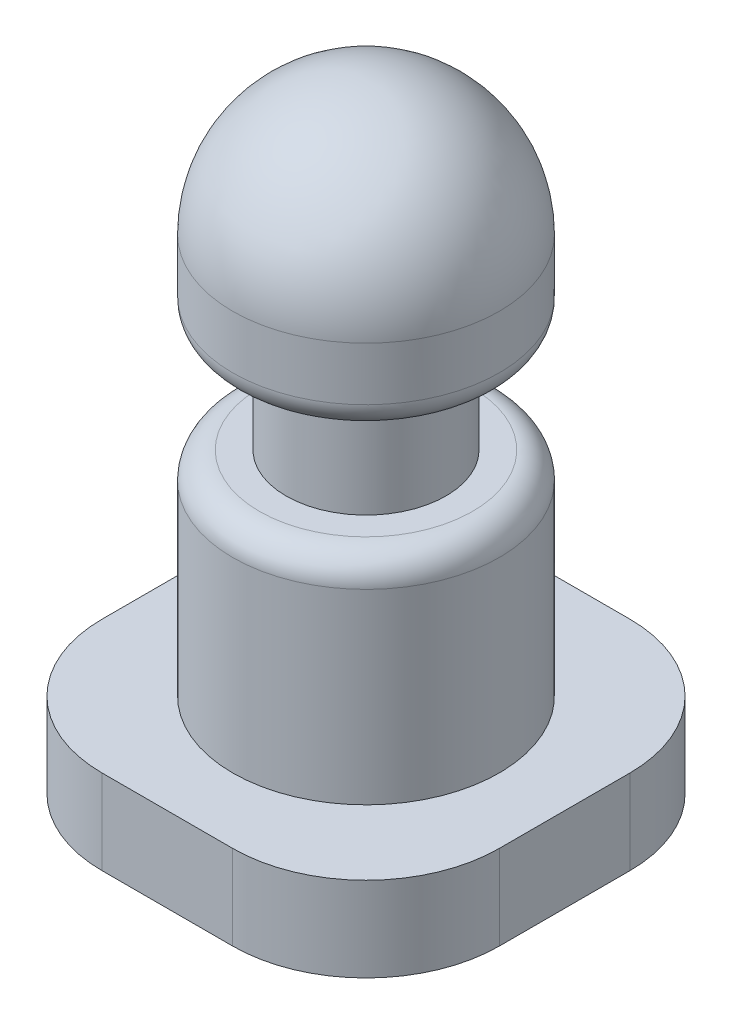
SolidWorks part; units mm, degrees
ref_plane "Front Plane" through (0, 0, 0) normal (0, 0, 1) x (1, 0, 0)
ref_plane "Top Plane" through (0, 0, 0) normal (0, 1, 0) x (1, 0, 0)
ref_plane "Right Plane" through (0, 0, 0) normal (1, 0, 0) x (0, 0, -1)
sketch "Sketch2" plane through (0, 0, 0) normal (0, 1, 0) x (1, 0, 0)
  line L0 (-14.9, -14.9) -> (14.9, -14.9)
  line L1 (-15, -15) -> (15, -15)
  line L2 (-15, -15) -> (-15, 15)
  line L3 (-15, 15) -> (15, 15)
  line L4 (15, -15) -> (15, 15)
  line L5 (-15, -15) -> (15, 15) construction
  line L6 (-15, 15) -> (15, -15) construction
  line L7 (14.9, -14.9) -> (14.9, 14.9)
  line L8 (-14.9, 14.9) -> (14.9, 14.9)
  line L9 (-14.9, -14.9) -> (-14.9, 14.9)
  point P0 (0, 0)
  dimension "D1" = 30
  dimension "D2" = 30
  dimension "D3" = 0.1
extrude "Boss-Extrude1" add sketch "Sketch2" along normal blind 6.35 contours L9 L0 L7 L8 region at (0, 0, 0)
fillet "Fillet1" radius 10 4 edges at (14.9, 3.175, 14.9) (-14.9, 3.175, 14.9) (-14.9, 3.175, -14.9) (14.9, 3.175, -14.9)
sketch "Sketch9" plane through (0, 6.35, 0) normal (0, 1, 0) x (1, 0, 0)
  circle A0 centre (0, 0) radius 10
  dimension "D1" = 20
extrude "Boss-Extrude6" add sketch "Sketch9" along normal blind 40 contours A0 region at (0, 6.35, 0)
fillet "Fillet5" radius 10 1 edges at (0, 46.35, 10)
ref_plane "Plane1" through (0, 26.35, 0) normal (0, 1, 0) x (1, 0, 0)
sketch "Sketch11" plane through (0, 26.35, 0) normal (0, 1, 0) x (1, 0, 0)
  circle A0 centre (0, 0) radius 10
  circle A1 centre (0, 0) radius 6
extrude "Cut-Extrude2" cut sketch "Sketch11" against normal blind 4 and the other way blind 4
fillet "Fillet6" radius 2 2 edges at (0, 30.35, 10) (0, 22.35, 10)
sketch "Sketch12" plane through (0, 0, 0) normal (0, -1, 0) x (1, 0, 0)
  circle A0 centre (0, 0) radius 2.1225
  dimension "D1" = 4.245
extrude "Cut-Extrude3" cut sketch "Sketch12" against normal blind 5
